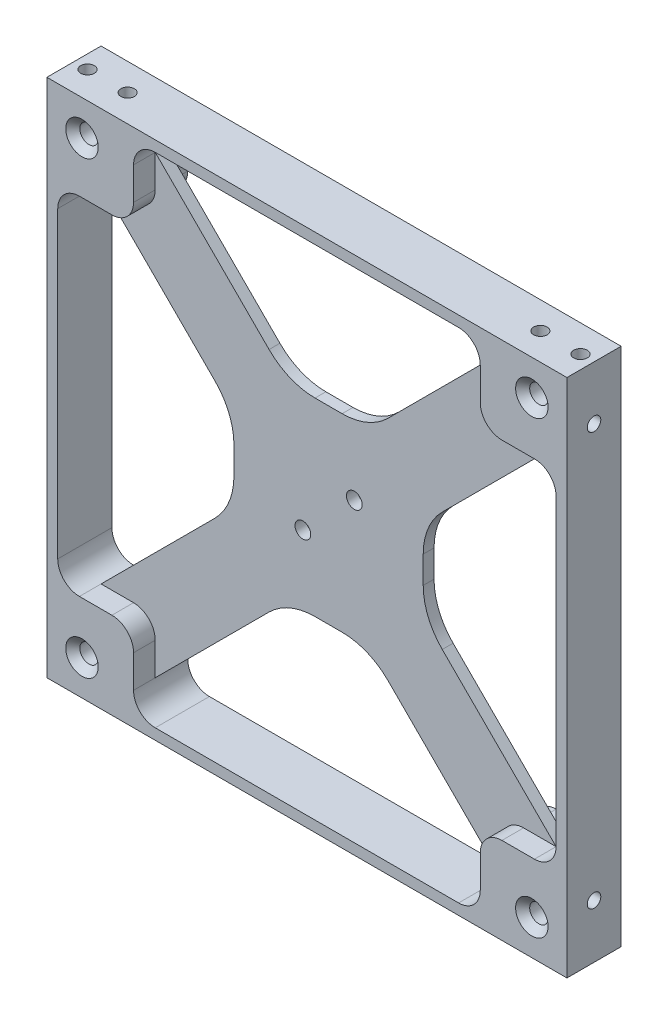
SolidWorks part; units mm, degrees
material "7075-T6 (SN)"
ref_plane "Front Plane" through (0, 0, 0) normal (0, 0, 1) x (1, 0, 0)
ref_plane "Top Plane" through (0, 0, 0) normal (0, 1, 0) x (1, 0, 0)
ref_plane "Right Plane" through (0, 0, 0) normal (1, 0, 0) x (0, 0, -1)
sketch "Construction Lines" plane through (0, 0, 0) normal (0, 0, 1) x (1, 0, 0)
  line L0 (0, 0) -> (0, -14.7163) construction
  line L1 (0, 0) -> (23.9312, 0) construction
sketch "Sketch3" plane through (0, 0, 0) normal (0, 0, 1) x (1, 0, 0)
  line L0 (0, 48) -> (48, 48)
  line L1 (0, 200000) -> (0, -200014.7163) construction
  line L2 (48, 48) -> (48, 0)
  line L3 (-200000, 0) -> (200023.9312, 0) construction
  line L4 (0, 46) -> (28, 46)
  line L5 (46, 28) -> (46, 0)
  line L6 (0, 48) -> (0, 46)
  line L7 (48, 0) -> (46, 0)
  line L8 (32, 42) -> (32, 36)
  line L9 (36, 32) -> (42, 32)
  line L11 (0, 46) -> (46, 46) construction
  line L12 (46, 46) -> (46, 0) construction
  arc A0 (28, 46) -> (32, 42) centre (28, 42) cw
  arc A1 (32, 36) -> (36, 32) centre (36, 36) ccw
  arc A2 (46, 28) -> (42, 32) centre (42, 28) ccw
  dimension "D6" = 4
  dimension "D1" = 48
  dimension "D2" = 48
  dimension "D4" = 16
  dimension "D5" = 16
  dimension "D3" = 2
extrude "BottomLayer" add sketch "Sketch3" along normal blind 4
sketch "TopHolePosition" plane through (0, 0, 4) normal (0, 0, 1) x (1, 0, 0)
  line L0 (0, 0) -> (48, 48) construction
sketch "Sketch6" plane through (0, 0, 4) normal (0, 0, 1) x (1, 0, 0)
  line L0 (0, 17.4706) -> (0, 0)
  line L1 (0, 0) -> (17.4706, 0)
  line L3 (0, 17.4706) -> (2.5, 17.4706)
  line L4 (0, 0) -> (48, 48) construction
  line L6 (17.4706, 0) -> (17.4706, 2.5)
  line L7 (38, 48) -> (10.9853, 20.9853)
  line L8 (48, 38) -> (20.9853, 10.9853)
  line L15 (48, 48) -> (0, 48) construction
  line L16 (48, 0) -> (48, 48) construction
  line L17 (38, 48) -> (48, 48)
  line L18 (48, 48) -> (48, 38)
  arc A1 (20.9853, 10.9853) -> (17.4706, 2.5) centre (29.4706, 2.5) ccw
  arc A2 (10.9853, 20.9853) -> (2.5, 17.4706) centre (2.5, 29.4706) cw
  dimension "D1" = 2.5
  dimension "D2" = 2.5
  dimension "D4" = 12
extrude "MiddleLayer" add sketch "Sketch6" along normal blind 2
sketch "Sketch10" plane through (0, 0, 6) normal (0, 0, 1) x (1, 0, 0)
  line L8 (48, 48) -> (0, 48)
  line L9 (48, 0) -> (48, 48)
  line L10 (46, 0) -> (48, 0)
  line L11 (46, 28) -> (46, 0)
  line L12 (36, 32) -> (42, 32)
  line L13 (32, 42) -> (32, 36)
  line L14 (0, 46) -> (28, 46)
  line L15 (0, 48) -> (0, 46)
  line L16 (48, 48) -> (0, 48)
  line L17 (48, 0) -> (48, 48)
  line L18 (46, 0) -> (48, 0)
  line L19 (46, 28) -> (46, 0)
  line L20 (36, 32) -> (42, 32)
  line L21 (32, 42) -> (32, 36)
  line L22 (0, 46) -> (28, 46)
  line L23 (0, 48) -> (0, 46)
  arc A3 (46, 28) -> (42, 32) centre (42, 28) ccw
  arc A4 (46, 28) -> (42, 32) centre (42, 28) ccw
  arc A5 (32, 36) -> (36, 32) centre (36, 36) ccw
  arc A6 (32, 36) -> (36, 32) centre (36, 36) ccw
  arc A7 (32, 42) -> (28, 46) centre (28, 42) ccw
  arc A8 (32, 42) -> (28, 46) centre (28, 42) ccw
  dimension "D1" = 0
extrude "FillUpLayer" add sketch "Sketch10" against normal blind 2
sketch "Sketch11" plane through (0, 0, 6) normal (0, 0, 1) x (1, 0, 0)
  line L8 (48, 48) -> (0, 48)
  line L9 (48, 0) -> (48, 48)
  line L10 (46, 0) -> (48, 0)
  line L11 (46, 28) -> (46, 0)
  line L12 (36, 32) -> (42, 32)
  line L13 (32, 42) -> (32, 36)
  line L14 (0, 46) -> (28, 46)
  line L15 (0, 48) -> (0, 46)
  line L16 (48, 48) -> (0, 48)
  line L17 (48, 0) -> (48, 48)
  line L18 (46, 0) -> (48, 0)
  line L19 (46, 28) -> (46, 0)
  line L20 (36, 32) -> (42, 32)
  line L21 (32, 42) -> (32, 36)
  line L22 (0, 46) -> (28, 46)
  line L23 (0, 48) -> (0, 46)
  arc A3 (46, 28) -> (42, 32) centre (42, 28) ccw
  arc A4 (46, 28) -> (42, 32) centre (42, 28) ccw
  arc A5 (32, 36) -> (36, 32) centre (36, 36) ccw
  arc A6 (32, 36) -> (36, 32) centre (36, 36) ccw
  arc A7 (32, 42) -> (28, 46) centre (28, 42) ccw
  arc A8 (32, 42) -> (28, 46) centre (28, 42) ccw
  dimension "D1" = 0
extrude "TopLayer" add sketch "Sketch11" along normal blind 4
sketch "HolePosition" plane through (0, 0, 10) normal (0, 0, 1) x (1, 0, 0)
  line L0 (0, 41.525) -> (41.525, 41.525) construction
  line L1 (0, 200000) -> (0, -200014.7163) construction
  line L2 (0, 0) -> (48, 48) construction
  line L3 (41.525, 41.525) -> (41.525, 0) construction
  line L4 (-200000, 0) -> (200023.9312, 0) construction
  dimension "D1" = 41.525
hole_wizard "M3 Clearance Hole1" positions "Sketch13" profile "Sketch14" hole size "M3" standard "ISO" end condition through all
sketch "Sketch13" plane through (0, 0, 10) normal (0, 0, 1) x (1, 0, 0)
  point P0 (41.525, 41.525)
sketch "Sketch14" plane through (41.525, 41.525, 10) normal (1, 0, 0) x (0, -1, 0)
  line L0 (0, 0) -> (0, 10)
  line L1 (0, 10) -> (1.7, 10)
  line L2 (1.7, 10) -> (1.7, 1.3)
  line L3 (1.7, 1.3) -> (3, 0)
  line L5 (3, 0) -> (0, 0)
  line L6 (-1.7, 1.3) -> (-3, 0) construction
  line L11 (0, -6.35) -> (0, 107.95) construction
  dimension "Thru Hole Dia." = 3.4
  dimension "Thru Hole Depth" = 10
  dimension "Near C'Sink Dia." = 6
  dimension "Near C'Sink Angle" = 90
ref_axis "Axis1" through (0, 0, -0.5) along (0, 0, 1)
sketch "M2HolePositions" plane through (0, 0, 6) normal (0, 0, 1) x (1, 0, 0)
  line L0 (0, 0) -> (48, 48) construction
  line L1 (0, 200000) -> (0, -200014.7163) construction
  line L2 (0, 0) -> (6.9513, -6.9513) construction
  line L3 (-200000, 0) -> (200023.9312, 0) construction
  line L4 (0, 4.75) -> (4.75, 4.75) construction
  line L5 (4.75, 4.75) -> (4.75, 0) construction
  point P11 (0, 0)
  dimension "D1" = 45
  dimension "D3" = 4.75
hole_wizard "M2.5 Clearance Hole1" positions "Sketch24" profile "Sketch25" hole size "M2.5" standard "ISO" end condition through all
sketch "Sketch24" plane through (0, 0, 6) normal (0, 0, 1) x (1, 0, 0)
  point P0 (4.75, 4.75)
sketch "Sketch25" plane through (4.75, 4.75, 6) normal (1, 0, 0) x (0, -1, 0)
  line L0 (0, 0) -> (0, 6)
  line L1 (0, 6) -> (1.45, 6)
  line L2 (1.45, 6) -> (1.45, 0)
  line L5 (1.45, 0) -> (0, 0)
  line L11 (0, -6.35) -> (0, 107.95) construction
  dimension "Thru Hole Dia." = 2.9
  dimension "Thru Hole Depth" = 6
pattern_circular "CirPattern1" count 4 every 90 about axis through (0, 0, -0.5) along (0, 0, 1) of "TopLayer", "FillUpLayer", "MiddleLayer", "BottomLayer", "M3 Clearance Hole1"
sketch "SidePlate Hole ZY" plane through (48, 0, 0) normal (1, 0, 0) x (0, 0, -1)
  line L0 (-5, 48) -> (-5, -48) construction
  line L1 (-10, 48) -> (0, 48) construction
  line L2 (-10, -48) -> (0, -48) construction
  line L3 (-10, 38.1) -> (-5, 38.1) construction
  line L4 (-10, -48) -> (-10, 48) construction
  dimension "D1" = 9.9
sketch "SidePlate&RailHole ZX" plane through (0, 48, 0) normal (0, 1, 0) x (1, 0, 0)
  line L0 (48, -5) -> (-48, -5) construction
  line L1 (-48, -10) -> (-48, 0) construction
  line L2 (45.5, -10) -> (45.5, -5) construction
  line L5 (48, -10) -> (-48, -10) construction
  line L7 (38.1, -10) -> (38.1, -5) construction
  line L8 (48, -10) -> (48, 0) construction
  dimension "D1" = 2.5
  dimension "D2" = 9.9
hole_wizard "Tap Drill M3 Side Plate" positions "Sketch20" profile "Sketch21" hole size "M3" standard "ISO"
sketch "Sketch20" plane through (48, 0, 0) normal (1, 0, 0) x (0, 0, -1)
  point P0 (-5, 38.1)
sketch "Sketch21" plane through (48, 38.1, 5) normal (0, 1, 0) x (0, 0, -1)
  line L0 (0, 0) -> (0, 5.7511)
  line L1 (0, 5.7511) -> (1.25, 5)
  line L2 (1.25, 5) -> (1.25, 0)
  line L5 (1.25, 0) -> (0, 0)
  line L10 (0, 5.7511) -> (-1.25, 5) construction
  line L11 (0, -6.35) -> (0, 107.95) construction
  dimension "Hole Dia." = 2.5
  dimension "Hole Depth" = 5
  dimension "Drill Angle" = 118
ref_plane "MirrorPlaneForM2.5" through (0, 0, 0) normal (-0.7071, -0.7071, 0) x (0.7071, -0.7071, 0)
mirror "Camera Holes" about plane through (0, 0, 0) normal (-0.7071, -0.7071, 0) of "M2.5 Clearance Hole1"
hole_wizard "Tap Drill M3 Side Plate " positions "Sketch26" profile "Sketch27" hole size "M3" standard "ISO"
sketch "Sketch26" plane through (0, 48, 0) normal (0, 1, 0) x (1, 0, 0)
  point P0 (38.1, -5)
sketch "Sketch27" plane through (38.1, 48, 5) normal (1, 0, 0) x (0, 0, 1)
  line L0 (0, 0) -> (0, 5.7511)
  line L1 (0, 5.7511) -> (1.25, 5)
  line L2 (1.25, 5) -> (1.25, 0)
  line L5 (1.25, 0) -> (0, 0)
  line L10 (0, 5.7511) -> (-1.25, 5) construction
  line L11 (0, -6.35) -> (0, 107.95) construction
  dimension "Hole Dia." = 2.5
  dimension "Hole Depth" = 5
  dimension "Drill Angle" = 118
hole_wizard "Tap Drill M3 Rail" positions "Sketch28" profile "Sketch29" hole size "M3" standard "ISO"
sketch "Sketch28" plane through (0, 48, 0) normal (0, 1, 0) x (1, 0, 0)
  point P0 (45.5, -5)
sketch "Sketch29" plane through (45.5, 48, 5) normal (1, 0, 0) x (0, 0, 1)
  line L0 (0, 0) -> (0, 5.7511)
  line L1 (0, 5.7511) -> (1.25, 5)
  line L2 (1.25, 5) -> (1.25, 0)
  line L5 (1.25, 0) -> (0, 0)
  line L10 (0, 5.7511) -> (-1.25, 5) construction
  line L11 (0, -6.35) -> (0, 107.95) construction
  dimension "Hole Dia." = 2.5
  dimension "Hole Depth" = 5
  dimension "Drill Angle" = 118
mirror "SidePlate and Rail Holes 1" about plane through (0, 0, 0) normal (1, 0, 0) of "Tap Drill M3 Side Plate", "Tap Drill M3 Rail", "Tap Drill M3 Side Plate "
mirror "Side Plate and Rail Holes 2" about plane through (0, 0, 0) normal (0, 1, 0) of "SidePlate and Rail Holes 1"
